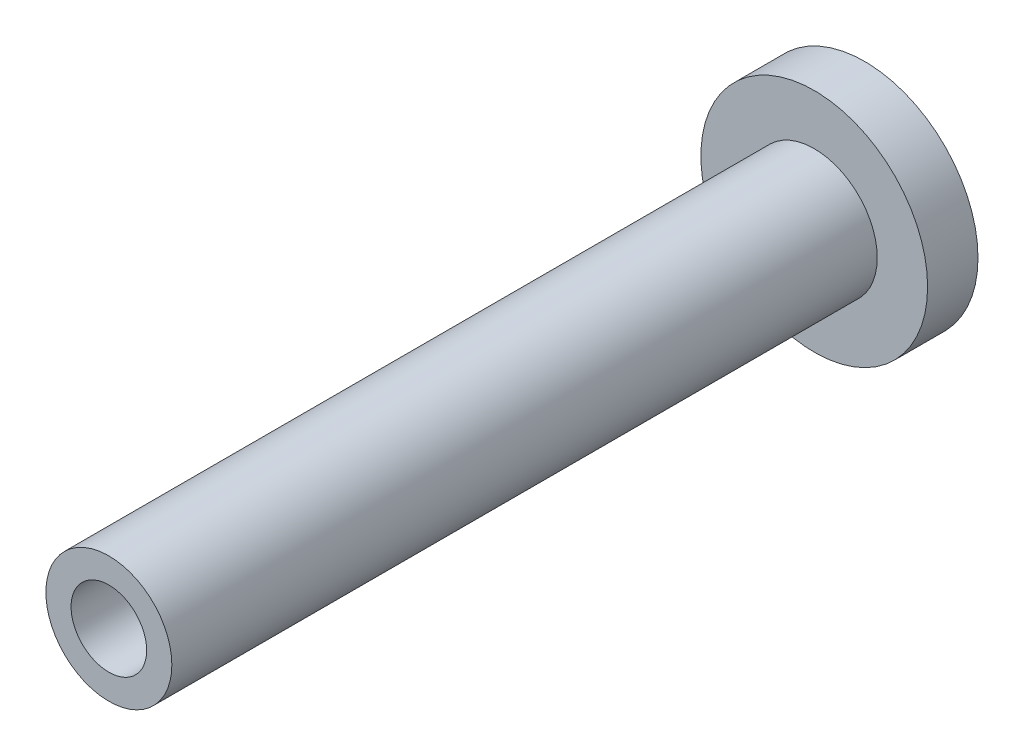
SolidWorks part; units mm, degrees
ref_plane "Front Plane" through (0, 0, 0) normal (0, 0, 1) x (1, 0, 0)
ref_plane "Top Plane" through (0, 0, 0) normal (0, 1, 0) x (1, 0, 0)
ref_plane "Right Plane" through (0, 0, 0) normal (1, 0, 0) x (0, 0, -1)
sketch "Sketch1" plane through (0, 0, 0) normal (0, 0, 1) x (1, 0, 0)
  circle A0 centre (0, 0) radius 2.5
  circle A1 centre (0, 0) radius 4.5
  dimension "D1" = 5
  dimension "D2" = 9
extrude "Boss-Extrude1" add sketch "Sketch1" along normal blind 2
sketch "Sketch5" plane through (0, 0, 2) normal (0, 0, 1) x (1, 0, 0)
  circle A0 centre (0, 0) radius 2.5
extrude "Boss-Extrude3" add sketch "Sketch5" along normal blind 28 separate body
sketch "Sketch6" plane through (0, 0, 30) normal (0, 0, 1) x (1, 0, 0)
  circle A0 centre (0, 0) radius 1.5
  dimension "D1" = 3
extrude "Cut-Extrude3" cut sketch "Sketch6" against normal blind 10
sketch "Sketch2" plane through (0, 0, 0) normal (0, 0, -1) x (-1, 0, 0)
  circle A1 centre (0, 0) radius 2.5
sketch "Sketch7" plane through (0, 0, 2) normal (0, 0, -1) x (-1, 0, 0)
  circle A0 centre (0, 0) radius 2.5
extrude "Boss-Extrude4" add sketch "Sketch7" along normal blind 1
fillet "Fillet1" radius 2 1 edges at (2.5, 0, 0)
